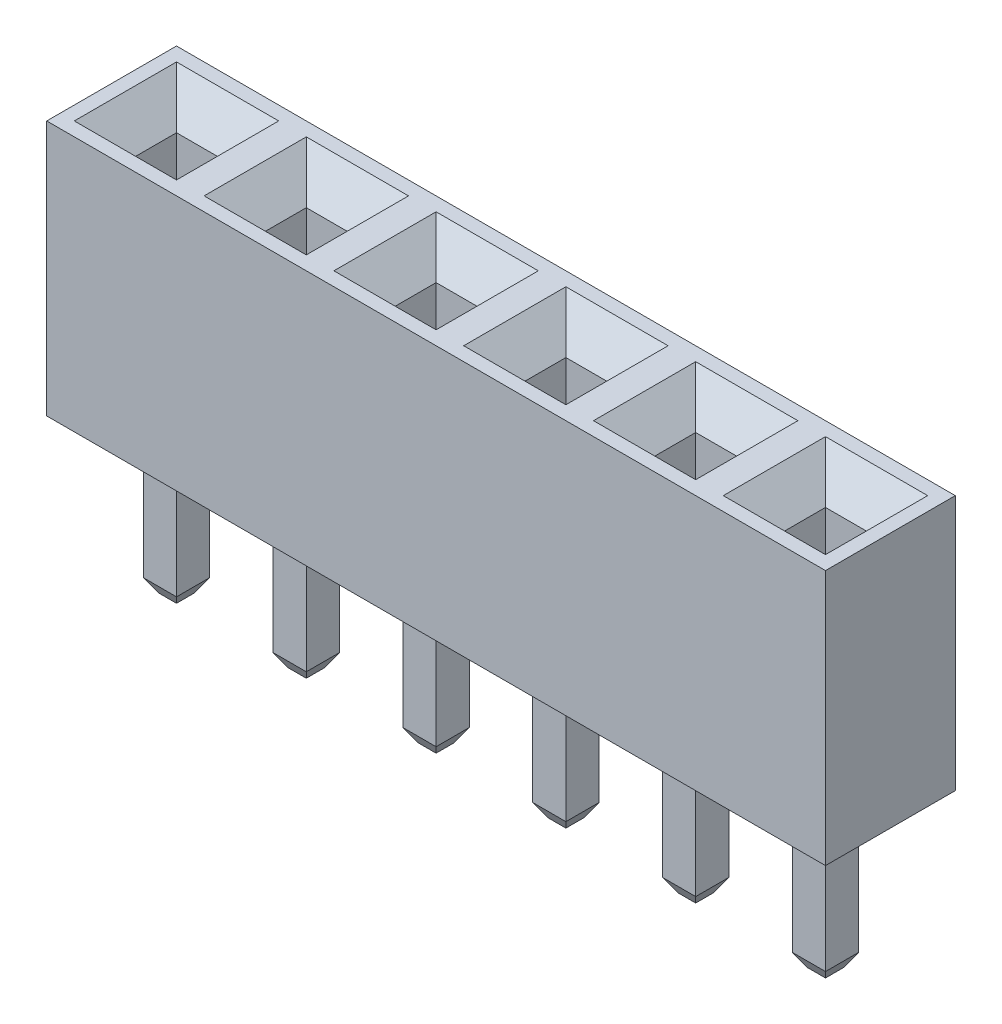
SolidWorks part; units mm, degrees
ref_plane "Front Plane" through (0, 0, 0) normal (0, 0, 1) x (1, 0, 0)
ref_plane "Top Plane" through (0, 0, 0) normal (0, 1, 0) x (1, 0, 0)
ref_plane "Right Plane" through (0, 0, 0) normal (1, 0, 0) x (0, 0, -1)
sketch "Sketch1" plane through (0, 0, 0) normal (0, 1, 0) x (1, 0, 0)
  line L1 (-1.27, 1.27) -> (1.27, 1.27)
  line L2 (-1.27, 1.27) -> (-1.27, -1.27)
  line L3 (-1.27, -1.27) -> (1.27, -1.27)
  line L4 (1.27, 1.27) -> (1.27, -1.27)
  line L5 (-1.27, 1.27) -> (1.27, -1.27) construction
  line L6 (-1.27, -1.27) -> (1.27, 1.27) construction
  point P0 (0, 0)
  dimension "D1" = 2.54
extrude "Boss-Extrude1" add sketch "Sketch1" along normal blind 5
sketch "Sketch2" plane through (0, 0, 0) normal (0, -1, 0) x (1, 0, 0)
  line L1 (-0.325, 0.325) -> (0.325, 0.325)
  line L2 (-0.325, 0.325) -> (-0.325, -0.325)
  line L3 (-0.325, -0.325) -> (0.325, -0.325)
  line L4 (0.325, 0.325) -> (0.325, -0.325)
  line L5 (-0.325, 0.325) -> (0.325, -0.325) construction
  line L6 (-0.325, -0.325) -> (0.325, 0.325) construction
  point P0 (0, 0)
  dimension "D1" = 0.65
extrude "Boss-Extrude2" add sketch "Sketch2" along normal blind 3
chamfer "Chamfer1" distance 0.15 angle 60 4 edges at (0, -3, -0.325) (-0.325, -3, 0) (0, -3, 0.325) (0.325, -3, 0) first distance on face at (0, -3, 0)
sketch "Sketch3" plane through (0, 5, 0) normal (0, 1, 0) x (1, 0, 0)
  line L1 (-0.4, 0.4) -> (0.4, 0.4)
  line L2 (-0.4, 0.4) -> (-0.4, -0.4)
  line L3 (-0.4, -0.4) -> (0.4, -0.4)
  line L4 (0.4, 0.4) -> (0.4, -0.4)
  line L5 (-0.4, 0.4) -> (0.4, -0.4) construction
  line L6 (-0.4, -0.4) -> (0.4, 0.4) construction
  point P0 (0, 0)
  dimension "D1" = 0.8
extrude "Cut-Extrude1" cut sketch "Sketch3" against normal blind 3
chamfer "Chamfer2" distance 0.6 angle 45 4 edges at (-0.4, 5, 0) (0, 5, 0.4) (0.4, 5, 0) (0, 5, -0.4)
pattern_linear "LPattern1" count 6 spacing 2.54 along (1, 0, 0) of "Boss-Extrude1", "Boss-Extrude2", "Cut-Extrude1", "Chamfer2", "Chamfer1"
ref_axis "Axis1" through (0, -5.675, 0) along (0, 1, 0)
